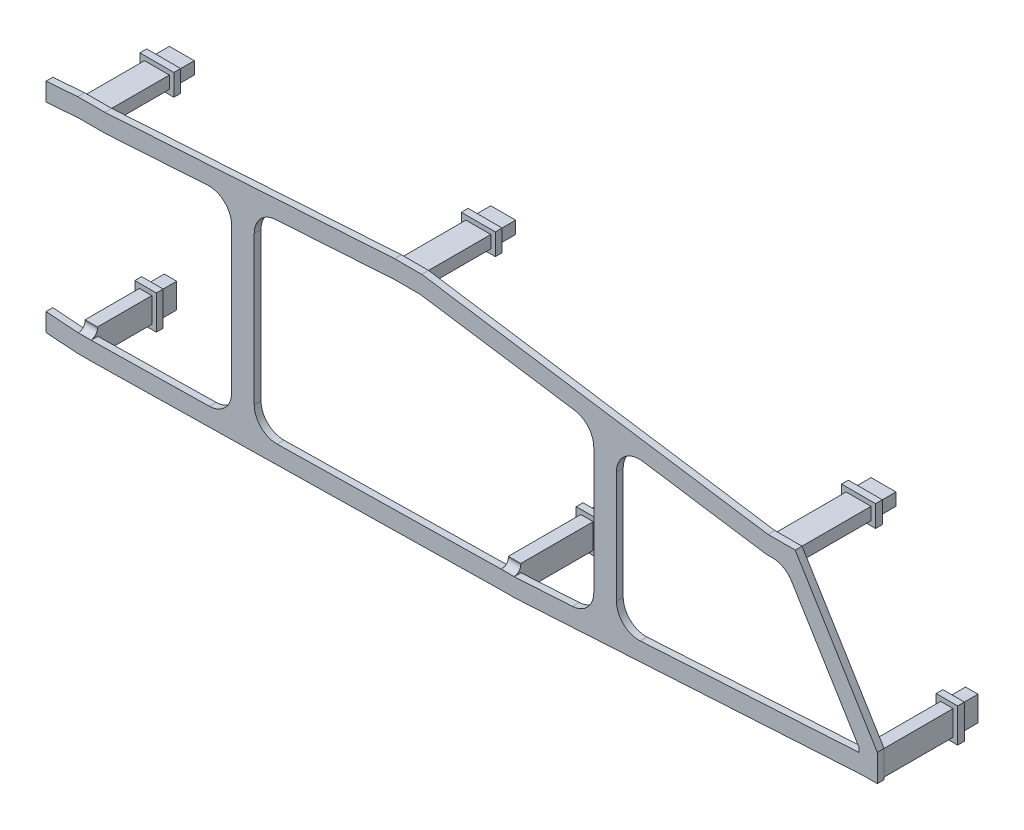
SolidWorks part; units mm, degrees
ref_plane "Front Plane" through (0, 0, 0) normal (0, 0, 1) x (1, 0, 0)
ref_plane "Top Plane" through (0, 0, 0) normal (0, 1, 0) x (1, 0, 0)
ref_plane "Right Plane" through (0, 0, 0) normal (1, 0, 0) x (0, 0, -1)
ref_plane "Plane11" through (0, 0, 7) normal (0, 0, 1) x (1, 0, 0)
ref_plane "Plane12" through (0, 0, 27) normal (0, 0, 1) x (1, 0, 0)
sketch "Sketch13" plane through (0, 0, 27) normal (0, 0, 1) x (1, 0, 0)
  line L0 (-277.75, -90) -> (-284.25, -90)
  line L1 (-284.25, -90) -> (-284.25, -78)
  line L2 (-284.25, -78) -> (-291, -3.25)
  line L3 (-291, -3.25) -> (-291, 3.25)
  line L4 (-291, 3.25) -> (-279, 3.25)
  line L5 (-279, 3.25) -> (-6, 3.25)
  line L6 (-6, 3.25) -> (6, 3.25)
  line L7 (6, 3.25) -> (32, 5.25)
  line L8 (32, 5.25) -> (44, 5.25)
  line L9 (44, 5.25) -> (172, 13.25)
  line L10 (172, 13.25) -> (184, 13.25)
  line L11 (184, 13.25) -> (337, -9.75)
  line L12 (337, -9.75) -> (349, -9.75)
  line L13 (349, -9.75) -> (385.25, -69)
  line L14 (385.25, -69) -> (385.25, -81)
  line L15 (385.25, -81) -> (378.75, -81)
  line L16 (378.75, -81) -> (225.25, -90)
  line L17 (225.25, -90) -> (218.75, -90)
  line L18 (218.75, -90) -> (38.25, -93)
  line L19 (38.25, -93) -> (31.75, -93)
  line L20 (31.75, -93) -> (4.25, -91)
  line L21 (4.25, -91) -> (-2.25, -91)
  line L22 (-2.25, -91) -> (-277.75, -90)
  line L23 (184, 13.25) -> (184, 6.75) construction
  point P4 (0, 0)
  point P47 (0, 0)
  point P48 (172, 13.25)
  point P50 (184, 13.25)
  point P53 (0, 0)
  point P54 (0, 0)
  point P55 (31.75, -93)
  point P57 (38.25, -93)
extrude "STUD LINK" add sketch "Sketch13" along normal blind 3
ref_plane "Plane1" through (0, 0, 0) normal (0, 0, 1) x (1, 0, 0)
ref_plane "Plane2" through (0, 0, -2) normal (0, 0, 1) x (1, 0, 0)
ref_plane "Plane3" through (0, 0, -4) normal (0, 0, 1) x (1, 0, 0)
ref_plane "Plane4" through (0, 0, 7) normal (0, 0, 1) x (1, 0, 0)
ref_plane "Plane5" through (0, 0, 0) normal (0, 0, 1) x (1, 0, 0)
ref_plane "Plane6" through (0, 0, -8) normal (0, 0, 1) x (1, 0, 0)
ref_plane "Plane7" through (0, 0, -7) normal (0, 0, 1) x (1, 0, 0)
ref_plane "Plane8" through (0, 0, -7) normal (0, 0, 1) x (1, 0, 0)
ref_plane "Plane9" through (0, 0, -6) normal (0, 0, 1) x (1, 0, 0)
ref_plane "Plane10" through (0, 0, -10) normal (0, 0, 1) x (1, 0, 0)
sketch "Sketch1" plane through (0, 0, 0) normal (0, 0, 1) x (1, 0, 0)
  line L8 (-5.5, 2.75) -> (-5.5, -2.75)
  line L9 (-5.5, -2.75) -> (5.5, -2.75)
  line L10 (5.5, -2.75) -> (5.5, 2.75)
  line L11 (5.5, 2.75) -> (-5.5, 2.75)
  line L12 (-5.5, 2.75) -> (-5.5, -2.75)
  line L13 (-5.5, -2.75) -> (5.5, -2.75)
  line L14 (5.5, -2.75) -> (5.5, 2.75)
  line L15 (5.5, 2.75) -> (-5.5, 2.75)
  dimension "D1" = 0.5
extrude "Boss-Extrude1" add sketch "Sketch1" against normal blind 8 and the other way up to next
sketch "Sketch2" plane through (0, 0, -2) normal (0, 0, 1) x (1, 0, 0)
  line L8 (43.5, 4.75) -> (32.5, 4.75)
  line L9 (43.5, -0.75) -> (43.5, 4.75)
  line L10 (32.5, -0.75) -> (43.5, -0.75)
  line L11 (32.5, 4.75) -> (32.5, -0.75)
  line L12 (43.5, 4.75) -> (32.5, 4.75)
  line L13 (43.5, -0.75) -> (43.5, 4.75)
  line L14 (32.5, -0.75) -> (43.5, -0.75)
  line L15 (32.5, 4.75) -> (32.5, -0.75)
  dimension "D1" = 0.5
extrude "Boss-Extrude2" add sketch "Sketch2" against normal blind 8 and the other way up to next separate body
sketch "Sketch3" plane through (0, 0, -4) normal (0, 0, 1) x (1, 0, 0)
  line L16 (183.5, 12.75) -> (172.5, 12.75)
  line L17 (183.5, 7.25) -> (183.5, 12.75)
  line L18 (172.5, 7.25) -> (183.5, 7.25)
  line L19 (172.5, 12.75) -> (172.5, 7.25)
  line L20 (183.5, 12.75) -> (172.5, 12.75)
  line L21 (183.5, 7.25) -> (183.5, 12.75)
  line L22 (172.5, 7.25) -> (183.5, 7.25)
  line L23 (172.5, 12.75) -> (172.5, 7.25)
  dimension "D1" = 0.5
extrude "Boss-Extrude3" add sketch "Sketch3" against normal blind 8 and the other way up to next separate body
sketch "Sketch4" plane through (0, 0, 7) normal (0, 0, 1) x (1, 0, 0)
  line L8 (3.75, -79.5) -> (-1.75, -79.5)
  line L9 (3.75, -90.5) -> (3.75, -79.5)
  line L10 (-1.75, -90.5) -> (3.75, -90.5)
  line L11 (-1.75, -79.5) -> (-1.75, -90.5)
  line L12 (3.75, -79.5) -> (-1.75, -79.5)
  line L13 (3.75, -90.5) -> (3.75, -79.5)
  line L14 (-1.75, -90.5) -> (3.75, -90.5)
  line L15 (-1.75, -79.5) -> (-1.75, -90.5)
  dimension "D1" = 0.5
extrude "Boss-Extrude4" add sketch "Sketch4" against normal blind 8 and the other way up to next separate body
sketch "Sketch5" plane through (0, 0, 0) normal (0, 0, 1) x (1, 0, 0)
  line L16 (32.25, -81.5) -> (32.25, -92.5)
  line L17 (37.75, -81.5) -> (32.25, -81.5)
  line L18 (37.75, -92.5) -> (37.75, -81.5)
  line L19 (32.25, -92.5) -> (37.75, -92.5)
  line L20 (32.25, -81.5) -> (32.25, -92.5)
  line L21 (37.75, -81.5) -> (32.25, -81.5)
  line L22 (37.75, -92.5) -> (37.75, -81.5)
  line L23 (32.25, -92.5) -> (37.75, -92.5)
  dimension "D1" = 0.5
extrude "Boss-Extrude5" add sketch "Sketch5" against normal blind 8 and the other way up to next separate body
sketch "Sketch6" plane through (0, 0, -8) normal (0, 0, 1) x (1, 0, 0)
  line L8 (224.75, -78.5) -> (219.25, -78.5)
  line L9 (219.25, -78.5) -> (219.25, -89.5)
  line L10 (219.25, -89.5) -> (224.75, -89.5)
  line L11 (224.75, -89.5) -> (224.75, -78.5)
  line L12 (224.75, -78.5) -> (219.25, -78.5)
  line L13 (219.25, -78.5) -> (219.25, -89.5)
  line L14 (219.25, -89.5) -> (224.75, -89.5)
  line L15 (224.75, -89.5) -> (224.75, -78.5)
  dimension "D1" = 0.5
extrude "Boss-Extrude6" add sketch "Sketch6" against normal blind 8 and the other way up to next separate body
sketch "Sketch7" plane through (0, 0, -7) normal (0, 0, 1) x (1, 0, 0)
  line L8 (348.5, -10.25) -> (337.5, -10.25)
  line L9 (348.5, -15.75) -> (348.5, -10.25)
  line L10 (337.5, -15.75) -> (348.5, -15.75)
  line L11 (337.5, -10.25) -> (337.5, -15.75)
  line L12 (348.5, -10.25) -> (337.5, -10.25)
  line L13 (348.5, -15.75) -> (348.5, -10.25)
  line L14 (337.5, -15.75) -> (348.5, -15.75)
  line L15 (337.5, -10.25) -> (337.5, -15.75)
  dimension "D1" = 0.5
extrude "Boss-Extrude7" add sketch "Sketch7" against normal blind 8 and the other way up to next separate body
sketch "Sketch8" plane through (0, 0, -7) normal (0, 0, 1) x (1, 0, 0)
  line L8 (384.75, -69.5) -> (379.25, -69.5)
  line L9 (384.75, -80.5) -> (384.75, -69.5)
  line L10 (379.25, -80.5) -> (384.75, -80.5)
  line L11 (379.25, -69.5) -> (379.25, -80.5)
  line L12 (384.75, -69.5) -> (379.25, -69.5)
  line L13 (384.75, -80.5) -> (384.75, -69.5)
  line L14 (379.25, -80.5) -> (384.75, -80.5)
  line L15 (379.25, -69.5) -> (379.25, -80.5)
  dimension "D1" = 0.5
extrude "Boss-Extrude8" add sketch "Sketch8" against normal blind 8 and the other way up to next separate body
sketch "Sketch9" plane through (0, 0, -6) normal (0, 0, 1) x (1, 0, 0)
  line L8 (-279.5, 2.75) -> (-290.5, 2.75)
  line L9 (-279.5, -2.75) -> (-279.5, 2.75)
  line L10 (-290.5, -2.75) -> (-279.5, -2.75)
  line L11 (-290.5, 2.75) -> (-290.5, -2.75)
  line L12 (-279.5, 2.75) -> (-290.5, 2.75)
  line L13 (-279.5, -2.75) -> (-279.5, 2.75)
  line L14 (-290.5, -2.75) -> (-279.5, -2.75)
  line L15 (-290.5, 2.75) -> (-290.5, -2.75)
  dimension "D1" = 0.5
extrude "Boss-Extrude9" add sketch "Sketch9" against normal blind 8 and the other way up to next separate body
sketch "Sketch10" plane through (0, 0, -10) normal (0, 0, 1) x (1, 0, 0)
  line L8 (-278.25, -78.5) -> (-283.75, -78.5)
  line L9 (-278.25, -89.5) -> (-278.25, -78.5)
  line L10 (-283.75, -89.5) -> (-278.25, -89.5)
  line L11 (-283.75, -78.5) -> (-283.75, -89.5)
  line L12 (-278.25, -78.5) -> (-283.75, -78.5)
  line L13 (-278.25, -89.5) -> (-278.25, -78.5)
  line L14 (-283.75, -89.5) -> (-278.25, -89.5)
  line L15 (-283.75, -78.5) -> (-283.75, -89.5)
  dimension "D1" = 0.5
extrude "Boss-Extrude10" add sketch "Sketch10" against normal blind 8 and the other way up to next (37 mm away) separate body
sketch "Sketch14" plane through (0, 0, 0) normal (0, 0, 1) x (1, 0, 0)
  line L8 (-7.5, -4.75) -> (7.5, -4.75)
  line L9 (7.5, -4.75) -> (7.5, 4.75)
  line L10 (7.5, 4.75) -> (-7.5, 4.75)
  line L11 (-7.5, 4.75) -> (-7.5, -4.75)
  line L12 (-7.5, -4.75) -> (7.5, -4.75)
  line L13 (7.5, -4.75) -> (7.5, 4.75)
  line L14 (7.5, 4.75) -> (-7.5, 4.75)
  line L15 (-7.5, 4.75) -> (-7.5, -4.75)
  dimension "D1" = 1.5
extrude "Boss-Extrude14" add sketch "Sketch14" along normal blind 3
sketch "Sketch15" plane through (0, 0, -2) normal (0, 0, 1) x (1, 0, 0)
  line L8 (45.5, 6.75) -> (30.5, 6.75)
  line L9 (30.5, 6.75) -> (30.5, -2.75)
  line L10 (30.5, -2.75) -> (45.5, -2.75)
  line L11 (45.5, -2.75) -> (45.5, 6.75)
  line L12 (45.5, 6.75) -> (30.5, 6.75)
  line L13 (30.5, 6.75) -> (30.5, -2.75)
  line L14 (30.5, -2.75) -> (45.5, -2.75)
  line L15 (45.5, -2.75) -> (45.5, 6.75)
  dimension "D1" = 1.5
extrude "Boss-Extrude15" add sketch "Sketch15" along normal blind 3
sketch "Sketch16" plane through (0, 0, -4) normal (0, 0, 1) x (1, 0, 0)
  line L16 (185.5, 14.75) -> (170.5, 14.75)
  line L17 (185.5, 5.25) -> (185.5, 14.75)
  line L18 (170.5, 5.25) -> (185.5, 5.25)
  line L19 (170.5, 14.75) -> (170.5, 5.25)
  line L20 (185.5, 14.75) -> (170.5, 14.75)
  line L21 (185.5, 5.25) -> (185.5, 14.75)
  line L22 (170.5, 5.25) -> (185.5, 5.25)
  line L23 (170.5, 14.75) -> (170.5, 5.25)
  dimension "D1" = 1.5
extrude "Boss-Extrude16" add sketch "Sketch16" along normal blind 3
sketch "Sketch17" plane through (0, 0, 7) normal (0, 0, 1) x (1, 0, 0)
  line L8 (5.75, -77.5) -> (-3.75, -77.5)
  line L9 (-3.75, -77.5) -> (-3.75, -92.5)
  line L10 (-3.75, -92.5) -> (5.75, -92.5)
  line L11 (5.75, -92.5) -> (5.75, -77.5)
  line L12 (5.75, -77.5) -> (-3.75, -77.5)
  line L13 (-3.75, -77.5) -> (-3.75, -92.5)
  line L14 (-3.75, -92.5) -> (5.75, -92.5)
  line L15 (5.75, -92.5) -> (5.75, -77.5)
  dimension "D1" = 1.5
extrude "Boss-Extrude17" add sketch "Sketch17" along normal blind 3
sketch "Sketch18" plane through (0, 0, 0) normal (0, 0, 1) x (1, 0, 0)
  line L8 (39.75, -79.5) -> (30.25, -79.5)
  line L9 (39.75, -94.5) -> (39.75, -79.5)
  line L10 (30.25, -94.5) -> (39.75, -94.5)
  line L11 (30.25, -79.5) -> (30.25, -94.5)
  line L16 (39.75, -79.5) -> (30.25, -79.5)
  line L17 (39.75, -94.5) -> (39.75, -79.5)
  line L18 (30.25, -94.5) -> (39.75, -94.5)
  line L19 (30.25, -79.5) -> (30.25, -94.5)
  dimension "D1" = 1.5
extrude "Boss-Extrude18" add sketch "Sketch18" along normal blind 3
sketch "Sketch19" plane through (0, 0, -8) normal (0, 0, 1) x (1, 0, 0)
  line L8 (226.75, -76.5) -> (217.25, -76.5)
  line L9 (226.75, -91.5) -> (226.75, -76.5)
  line L10 (217.25, -91.5) -> (226.75, -91.5)
  line L11 (217.25, -76.5) -> (217.25, -91.5)
  line L12 (226.75, -76.5) -> (217.25, -76.5)
  line L13 (226.75, -91.5) -> (226.75, -76.5)
  line L14 (217.25, -91.5) -> (226.75, -91.5)
  line L15 (217.25, -76.5) -> (217.25, -91.5)
  dimension "D1" = 1.5
extrude "Boss-Extrude19" add sketch "Sketch19" along normal blind 3
sketch "Sketch20" plane through (0, 0, -7) normal (0, 0, 1) x (1, 0, 0)
  line L8 (350.5, -8.25) -> (335.5, -8.25)
  line L9 (335.5, -8.25) -> (335.5, -17.75)
  line L10 (335.5, -17.75) -> (350.5, -17.75)
  line L11 (350.5, -17.75) -> (350.5, -8.25)
  line L12 (350.5, -8.25) -> (335.5, -8.25)
  line L13 (335.5, -8.25) -> (335.5, -17.75)
  line L14 (335.5, -17.75) -> (350.5, -17.75)
  line L15 (350.5, -17.75) -> (350.5, -8.25)
  dimension "D1" = 1.5
extrude "Boss-Extrude20" add sketch "Sketch20" along normal blind 3
sketch "Sketch21" plane through (0, 0, -7) normal (0, 0, 1) x (1, 0, 0)
  line L8 (386.75, -67.5) -> (377.25, -67.5)
  line L9 (386.75, -82.5) -> (386.75, -67.5)
  line L10 (377.25, -82.5) -> (386.75, -82.5)
  line L11 (377.25, -67.5) -> (377.25, -82.5)
  line L12 (386.75, -67.5) -> (377.25, -67.5)
  line L13 (386.75, -82.5) -> (386.75, -67.5)
  line L14 (377.25, -82.5) -> (386.75, -82.5)
  line L15 (377.25, -67.5) -> (377.25, -82.5)
  dimension "D1" = 1.5
extrude "Boss-Extrude21" add sketch "Sketch21" along normal blind 3
sketch "Sketch22" plane through (0, 0, -6) normal (0, 0, 1) x (1, 0, 0)
  line L8 (-277.5, 4.75) -> (-292.5, 4.75)
  line L9 (-277.5, -4.75) -> (-277.5, 4.75)
  line L10 (-292.5, -4.75) -> (-277.5, -4.75)
  line L11 (-292.5, 4.75) -> (-292.5, -4.75)
  line L12 (-277.5, 4.75) -> (-292.5, 4.75)
  line L13 (-277.5, -4.75) -> (-277.5, 4.75)
  line L14 (-292.5, -4.75) -> (-277.5, -4.75)
  line L15 (-292.5, 4.75) -> (-292.5, -4.75)
  dimension "D1" = 1.5
extrude "Boss-Extrude22" add sketch "Sketch22" along normal blind 3
sketch "Sketch23" plane through (0, 0, -10) normal (0, 0, 1) x (1, 0, 0)
  line L15 (-276.25, -76.5) -> (-285.75, -76.5)
  line L16 (-285.75, -76.5) -> (-285.75, -91.5)
  line L17 (-276.25, -91.5) -> (-276.25, -76.5)
  line L18 (-285.75, -91.5) -> (-276.25, -91.5)
  line L19 (-276.25, -76.5) -> (-285.75, -76.5)
  line L20 (-285.75, -76.5) -> (-285.75, -91.5)
  line L21 (-276.25, -91.5) -> (-276.25, -76.5)
  line L22 (-285.75, -91.5) -> (-276.25, -91.5)
  dimension "D1" = 1.5
extrude "Boss-Extrude23" add sketch "Sketch23" along normal blind 3
sketch "Sketch24" plane through (0, 0, 30) normal (0, 0, 1) x (1, 0, 0)
  line L42 (-276.25, -82.0054) -> (-2.2355, -83)
  line L43 (-2.2355, -83) -> (4.5405, -83)
  line L44 (4.5405, -83) -> (32.0405, -85)
  line L45 (32.0405, -85) -> (38.1835, -85)
  line L46 (38.1835, -85) -> (218.6835, -82)
  line L47 (218.6835, -82) -> (225.0157, -82)
  line L48 (225.0157, -82) -> (377.25, -73.0742)
  line L49 (377.25, -73.0742) -> (377.25, -71.2531)
  line L50 (377.25, -71.2531) -> (344.516, -17.75)
  line L51 (344.516, -17.75) -> (336.4021, -17.75)
  line L52 (336.4021, -17.75) -> (183.4021, 5.25)
  line L53 (183.4021, 5.25) -> (172.2498, 5.25)
  line L54 (172.2498, 5.25) -> (44.2498, -2.75)
  line L55 (44.2498, -2.75) -> (32.3072, -2.75)
  line L56 (32.3072, -2.75) -> (6.3072, -4.75)
  line L57 (6.3072, -4.75) -> (-282.832, -4.75)
  line L58 (-282.832, -4.75) -> (-276.25, -77.6395)
  line L59 (-276.25, -77.6395) -> (-276.25, -82.0054)
  line L60 (-276.25, -82.0054) -> (-2.2355, -83)
  line L61 (-2.2355, -83) -> (4.5405, -83)
  line L62 (4.5405, -83) -> (32.0405, -85)
  line L63 (32.0405, -85) -> (38.1835, -85)
  line L64 (38.1835, -85) -> (218.6835, -82)
  line L65 (218.6835, -82) -> (225.0157, -82)
  line L66 (225.0157, -82) -> (377.25, -73.0742)
  line L67 (377.25, -73.0742) -> (377.25, -71.2531)
  line L68 (377.25, -71.2531) -> (344.516, -17.75)
  line L69 (344.516, -17.75) -> (336.4021, -17.75)
  line L70 (336.4021, -17.75) -> (183.4021, 5.25)
  line L71 (183.4021, 5.25) -> (172.2498, 5.25)
  line L72 (172.2498, 5.25) -> (44.2498, -2.75)
  line L73 (44.2498, -2.75) -> (32.3072, -2.75)
  line L74 (32.3072, -2.75) -> (6.3072, -4.75)
  line L75 (6.3072, -4.75) -> (-282.832, -4.75)
  line L76 (-282.832, -4.75) -> (-276.25, -77.6395)
  line L77 (-276.25, -77.6395) -> (-276.25, -82.0054)
  dimension "D1" = 8
extrude "Cut-Extrude1" cut sketch "Sketch24" against normal blind 3
ref_plane "Plane13" through (0, -50, 0) normal (0, 1, 0) x (1, 0, 0)
sketch "Sketch25" plane through (0, -50, 0) normal (0, 1, 0) x (1, 0, 0)
  line L0 (6, -27) -> (-291, -27) construction
  line L1 (-210, -27) -> (-200, -27)
  line L2 (-210, -27) -> (-210, -30)
  line L3 (-210, -30) -> (-200, -30)
  line L4 (-200, -27) -> (-200, -30)
  line L5 (6, -30) -> (-291, -30) construction
  line L6 (172, -27) -> (44, -27) construction
  line L7 (-50, -27) -> (-40, -27)
  line L8 (-50, -27) -> (-50, -30)
  line L9 (-50, -30) -> (-40, -30)
  line L10 (-40, -27) -> (-40, -30)
  line L11 (100, -27) -> (110, -27)
  line L12 (100, -27) -> (100, -30)
  line L13 (100, -30) -> (110, -30)
  line L14 (110, -27) -> (110, -30)
  line L15 (172, -30) -> (44, -30) construction
  line L16 (337, -27) -> (184, -27) construction
  line L17 (260, -27) -> (270, -27)
  line L18 (260, -27) -> (260, -30)
  line L19 (260, -30) -> (270, -30)
  line L20 (270, -27) -> (270, -30)
  line L21 (337, -30) -> (184, -30) construction
  dimension "D1" = 10
  dimension "D2" = 150
  dimension "D3" = 40
  dimension "D4" = 100
  dimension "D5" = 150
extrude "Boss-Extrude24" add sketch "Sketch25" along normal up to next and the other way up to next
fillet "Fillet1" radius 3 3 edges at (222, -82, 27) (1, -83, 27) (35, -85, 27)
fillet "Fillet2" radius 10 20 edges at (-210, -82.2459, 28.5) (-210, -4.75, 28.5) (-282.832, -4.75, 28.5) (-276.25, -82.0054, 28.5) (100, -83.9726, 28.5) (100, 0.7344, 28.5) (-50, -4.75, 28.5) (-50, -82.8266, 28.5) (-40, -82.8629, 28.5) (-200, -82.2822, 28.5) (-200, -4.75, 28.5) (-40, -4.75, 28.5) (110, 1.3594, 28.5) (110, -83.8064, 28.5) (270, -79.3625, 28.5) (260, -79.9488, 28.5) (260, -6.2647, 28.5) (270, -7.768, 28.5) (336.4021, -17.75, 28.5) (344.516, -17.75, 28.5)
ref_plane "Plane14" through (18, 0, 0) normal (-1, 0, 0) x (0, 0, 1)
sketch "Sketch26" plane through (18, 0, 0) normal (-1, 0, 0) x (0, 0, 1)
  line L1 (-177.7155, 99.6631) -> (210.2216, 99.6631)
  line L2 (-177.7155, 99.6631) -> (-177.7155, -244.2201)
  line L3 (-177.7155, -244.2201) -> (210.2216, -244.2201)
  line L4 (210.2216, 99.6631) -> (210.2216, -244.2201)
extrude "Cut-Extrude2" cut sketch "Sketch26" along normal through all
